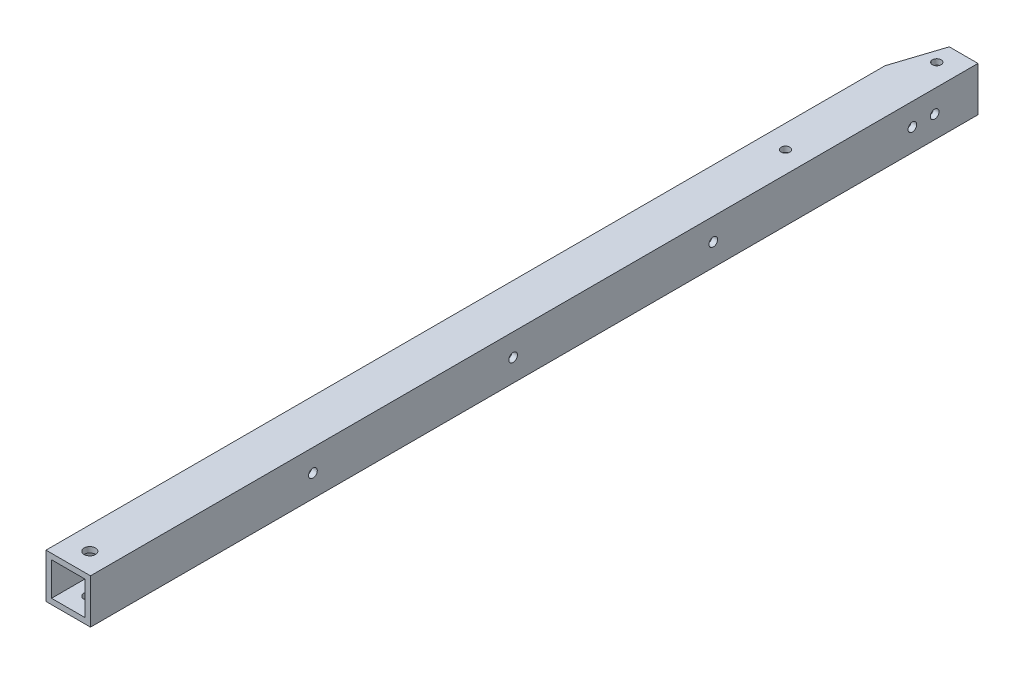
SolidWorks part; units mm, degrees
material "6061 Alloy"
ref_plane "Front Plane" through (0, 0, 0) normal (0, 0, 1) x (1, 0, 0)
ref_plane "Top Plane" through (0, 0, 0) normal (0, 1, 0) x (1, 0, 0)
ref_plane "Right Plane" through (0, 0, 0) normal (1, 0, 0) x (0, 0, -1)
sketch "Sketch1" plane through (0, 0, 0) normal (0, 0, 1) x (1, 0, 0)
  line L0 (-9.525, 9.525) -> (9.525, 9.525)
  line L2 (-12.7, 12.7) -> (12.7, 12.7)
  line L3 (-12.7, 12.7) -> (-12.7, -12.7)
  line L4 (-12.7, -12.7) -> (12.7, -12.7)
  line L5 (12.7, 12.7) -> (12.7, -12.7)
  line L10 (9.525, 9.525) -> (9.525, -9.525)
  line L11 (-9.525, -9.525) -> (9.525, -9.525)
  line L12 (-9.525, 9.525) -> (-9.525, -9.525)
  point P12 (0, 12.7)
  point P14 (12.7, 0)
  dimension "Wall Thickness" = 3.175
  dimension "Outside Width" = 25.4
  dimension "Outside Height" = 25.4
  dimension "Inside Height" = 19.05
  dimension "Inside Width" = 19.05
sketch "Sketch2" plane through (0, 0, 0) normal (1, 0, 0) x (0, 0, -1)
  line L0 (260.35, 0) -> (-260.35, 0)
  point P4 (0, 0)
  point P7 (-260.35, 0)
  point P10 (260.35, 0)
  dimension "Length" = 520.7
sketch "Sketch3" plane through (0, 0, 0) normal (0, 0, 1) x (1, 0, 0)
  line L21 (12.7, 12.7) -> (-12.7, 12.7)
  line L22 (12.7, -12.7) -> (12.7, 12.7)
  line L23 (-12.7, -12.7) -> (12.7, -12.7)
  line L24 (-12.7, 12.7) -> (-12.7, -12.7)
  line L25 (12.7, 12.7) -> (-12.7, 12.7)
  line L26 (12.7, -12.7) -> (12.7, 12.7)
  line L27 (-12.7, -12.7) -> (12.7, -12.7)
  line L28 (-12.7, 12.7) -> (-12.7, -12.7)
  line L29 (9.525, 9.525) -> (-9.525, 9.525)
  line L30 (9.525, -9.525) -> (9.525, 9.525)
  line L31 (-9.525, -9.525) -> (9.525, -9.525)
  line L32 (-9.525, 9.525) -> (-9.525, -9.525)
  line L33 (9.525, 9.525) -> (-9.525, 9.525)
  line L34 (9.525, -9.525) -> (9.525, 9.525)
  line L35 (-9.525, -9.525) -> (9.525, -9.525)
  line L36 (-9.525, 9.525) -> (-9.525, -9.525)
  dimension "D1" = 0
  dimension "D2" = 0
extrude "Boss-Extrude1" add sketch "Sketch3" along normal up to vertex (260.35 mm away) and the other way up to vertex (260.35 mm away) up to point (0, 0, 260.35) other way up to point (0, 0, -260.35)
sketch "Drawing Reference" plane through (0, 0, 0) normal (1, 0, 0) x (0, 0, -1)
  line L0 (-260.35, 0) -> (260.35, 0) construction
  line L1 (0, -12.7) -> (0, 12.7) construction
  line L2 (-260.35, -12.7) -> (260.35, -12.7) construction
  line L5 (-260.35, 12.7) -> (260.35, 12.7) construction
  point P7 (-242.062, 0)
  point P8 (242.062, 0)
  dimension "D1" = 18.288
sketch "Sketch4" plane through (0, 12.7, 0) normal (0, 1, 0) x (1, 0, 0)
  line L7 (-12.7, 218.6635) -> (-12.7, 260.35)
  line L10 (-12.7, -260.35) -> (-12.7, 260.35) construction
  line L11 (-12.7, 260.35) -> (12.7, 260.35)
  line L12 (12.7, 260.35) -> (12.7, 246.38)
  line L13 (12.7, -260.35) -> (12.7, 260.35) construction
  line L14 (12.7, 246.38) -> (-3.6932, 246.38)
  line L15 (-3.6932, 246.38) -> (-12.7, 218.6635)
  dimension "D1" = 13.97
  dimension "D2" = 41.6865
  dimension "D3" = 9.0068
extrude "Cut-Extrude1" cut sketch "Sketch4" against normal blind 25.4
sketch "Sketch5" plane through (0, -12.7, 0) normal (0, -1, 0) x (1, 0, 0)
  circle A0 centre (-0.278, -174.7033) radius 9.525
extrude "Cut-Extrude2" cut sketch "Sketch5" against normal blind 3.175
sketch "Sketch6" plane through (12.7, 0, 0) normal (1, 0, 0) x (0, 0, -1)
  line L0 (246.38, 0) -> (208.915, 0) construction
  line L1 (246.38, -12.7) -> (246.38, 12.7) construction
  line L2 (208.915, 0) -> (221.615, 0) construction
  dimension "D1" = 37.465
hole_wizard "#10 Clearance Hole2" positions "Sketch9" profile "Sketch10" hole size "#10" standard "ANSI Inch" end condition through all
sketch "Sketch9" plane through (0, 12.7, 0) normal (0, 1, 0) x (1, 0, 0)
  point P0 (0.3797, 148.7865)
  point P3 (0.3831, 235.1731)
sketch "Sketch10" plane through (0.3797, 12.7, -148.7865) normal (1, 0, 0) x (0, 0, 1)
  line L0 (0, 0) -> (0, 25.4)
  line L1 (0, 25.4) -> (2.4892, 25.4)
  line L2 (2.4892, 25.4) -> (2.4892, 0)
  line L5 (2.4892, 0) -> (0, 0)
  line L11 (0, -6.35) -> (0, 107.95) construction
  dimension "Thru Hole Dia." = 4.9784
  dimension "Thru Hole Depth" = 25.4
sketch "Sketch20" plane through (0, 12.7, 0) normal (0, 1, 0) x (1, 0, 0)
  line L0 (0.364, -248.3815) -> (0.364, -260.35) construction
  line L1 (12.7, -260.35) -> (-12.7, -260.35) construction
  circle A0 centre (0.364, -248.3815) radius 3.175 construction
  point P2 (0, -260.35)
  dimension "D1" = 11.9685
  dimension "D2" = 0.364
hole_wizard "1/4 Clearance Hole2" positions "Sketch13" profile "Sketch14" hole size "1/4" standard "ANSI Inch" end condition through all
sketch "Sketch13" plane through (0, 12.7, 0) normal (0, 1, 0) x (1, 0, 0)
  point P0 (0.364, -248.3815)
sketch "Sketch14" plane through (0.364, 12.7, 248.3815) normal (1, 0, 0) x (0, 0, 1)
  line L0 (0, 0) -> (0, 25.4)
  line L1 (0, 25.4) -> (3.2639, 25.4)
  line L2 (3.2639, 25.4) -> (3.2639, 0)
  line L5 (3.2639, 0) -> (0, 0)
  line L11 (0, -6.35) -> (0, 107.95) construction
  dimension "Thru Hole Dia." = 6.5278
  dimension "Thru Hole Depth" = 25.4
hole_wizard "#10 Clearance Hole3" positions "Sketch15" profile "Sketch16" hole size "#10" standard "ANSI Inch"
sketch "Sketch15" plane through (12.7, 0, 0) normal (1, 0, 0) x (0, 0, -1)
  point P0 (221.615, 0)
  point P4 (208.915, 0)
sketch "Sketch16" plane through (12.7, 0, -221.615) normal (0, 1, 0) x (0, 0, -1)
  line L0 (0, 0) -> (0, 6.5757)
  line L1 (0, 6.5757) -> (2.4892, 5.08)
  line L2 (2.4892, 5.08) -> (2.4892, 0)
  line L5 (2.4892, 0) -> (0, 0)
  line L10 (0, 6.5757) -> (-2.4892, 5.08) construction
  line L11 (0, -6.35) -> (0, 107.95) construction
  dimension "Hole Dia." = 4.9784
  dimension "Hole Depth" = 5.08
  dimension "Drill Angle" = 118
sketch "Sketch17" plane through (12.7, 0, 0) normal (1, 0, 0) x (0, 0, -1)
  line L0 (-260.35, 0) -> (-133.35, 0) construction
  line L1 (-260.35, -12.7) -> (-260.35, 12.7) construction
  line L2 (-133.35, 0) -> (-19.05, 0) construction
  line L3 (-19.05, 0) -> (95.25, 0) construction
  dimension "D1" = 127
  dimension "D2" = 114.3
  dimension "D3" = 114.3
hole_wizard "#10 Clearance Hole4" positions "Sketch18" profile "Sketch19" hole size "#10" standard "ANSI Inch" end condition through all
sketch "Sketch18" plane through (12.7, 0, 0) normal (1, 0, 0) x (0, 0, -1)
  point P0 (-133.35, 0)
  point P3 (-19.05, 0)
  point P6 (95.25, 0)
sketch "Sketch19" plane through (12.7, 0, 133.35) normal (0, 1, 0) x (0, 0, -1)
  line L0 (0, 0) -> (0, 25.4)
  line L1 (0, 25.4) -> (2.4892, 25.4)
  line L2 (2.4892, 25.4) -> (2.4892, 0)
  line L5 (2.4892, 0) -> (0, 0)
  line L11 (0, -6.35) -> (0, 107.95) construction
  dimension "Thru Hole Dia." = 4.9784
  dimension "Thru Hole Depth" = 25.4
equation "\"D1@Drawing Reference\"=\"Outside Width@Sketch1\" * 0.72"
